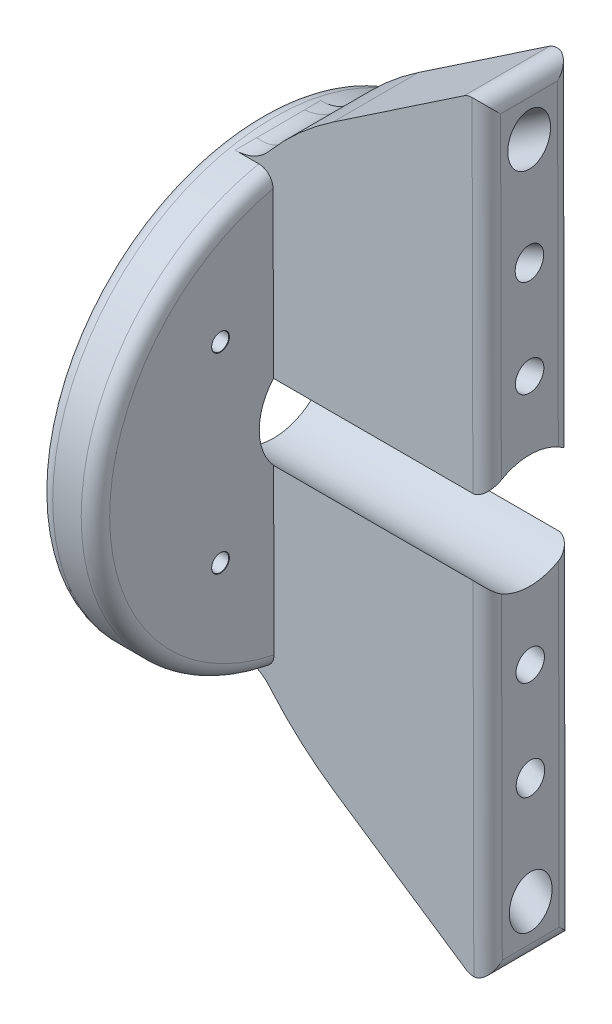
SolidWorks part; units mm, degrees
note: '?' marks a value the reader was unsure of.
ref_plane "前视基准面" through (0, 0, 0) normal (0, 0, 1) x (1, 0, 0)
ref_plane "上视基准面" through (0, 0, 0) normal (0, 1, 0) x (1, 0, 0)
ref_plane "右视基准面" through (0, 0, 0) normal (1, 0, 0) x (0, 0, -1)
other "图形1"
sketch "草图5" plane through (-19, 0, 0) normal (-1, 0, 0) x (0, 0, 1)
  circle A0 centre (0, 0) radius 15.5
  dimension "D1" = 31
extrude "凸台-拉伸3" add sketch "草图5" against normal blind 4
ref_axis "基准轴1" through (0, -27.6387, 2) along (0, 0, -1)?
ref_plane "基准面1" through (0, 0.0045, -2.0046) normal (0, 0.0023, -1) x (0, 1, 0.0023)
ref_point "点1"
ref_axis "基准轴2" through (0, 27.6387, 2) along (0, 0, -1)?
ref_axis "基准轴3" through (-19, 14.825, 17.05) along (0, 0, -1)?
ref_point "点2"
ref_point "点3"
ref_axis "基准轴4" through (-19, -14.825, -17.05) along (0, 0, 1)?
ref_point "点4"
sketch "草图15" plane through (0, 0.0045, -2.0046) normal (0, 0.0023, -1) x (0, 1, 0.0023)
  line L0 (-27.6433, 0) -> (27.6342, 0)
  line L1 (27.6342, 0) -> (14.8205, -19)
  line L2 (14.8205, -19) -> (-14.8296, -19)
  line L3 (-14.8296, -19) -> (-27.6433, 0)
  line L4 (-18.7273, -13.2205) -> (-11.9872, -19)
  line L5 (0, 0) -> (-0.0045, -19) construction
  line L6 (-15.5, -19) -> (15.5, -19) construction
  line L7 (18.721, -13.2295) -> (11.9781, -19.0057)
extrude "凸台-拉伸4" add sketch "草图15" against normal blind 5 and the other way blind 1 contours L5 L0 L3 L4 L2 | L0 L5 L2 L7 L1
sketch "草图16" plane through (0, 0, 0) normal (1, 0, 0) x (0, 0, -1)
  line L0 (-2.9954, -0.0113) -> (2.0046, -0.0113) construction
  line L2 (2.0265, -9.706) -> (1.9827, 9.7151) construction
  line L3 (-2.933, -27.65) -> (-3.0578, 27.6274) construction
  circle A0 centre (0, 0) radius 4
  point P2 (0, 0)
  dimension "D1" = 8
extrude "切除-拉伸2" cut sketch "草图16" against normal through all
sketch "草图17" plane through (-19, 0, 0) normal (-1, 0, 0) x (0, 0, 1)
  circle A0 centre (0, 0) radius 6
  dimension "D1" = 12
extrude "切除-拉伸3" cut sketch "草图17" against normal blind 1
sketch "草图20" plane through (-15, 0, 0) normal (1, 0, 0) x (0, 0, -1)
  line L0 (-9.5, 0) -> (9.5, 0) construction
  line L1 (0, 9.5) -> (0, -9.5) construction
  line L2 (-6.7175, 6.7175) -> (6.7175, -6.7175) construction
  line L3 (-6.7175, -6.7175) -> (6.7175, 6.7175) construction
  line L4 (0, 9.5) -> (9.5, 0) construction
  circle A0 centre (0, 0) radius 9.5 construction
  circle A1 centre (-6.7175, 6.7175) radius 0.5
  circle A2 centre (6.7175, 6.7175) radius 0.5
  circle A3 centre (6.7175, -6.7175) radius 0.5
  circle A4 centre (-6.7175, -6.7175) radius 0.5
  point P21 (0, 0)
  dimension "D1" = 19
  dimension "D3" = 1
  dimension "D2" = 4
hole_wizard "M1 间隙孔1" positions "草图21" profile "草图22" hole size "M1" standard "GB" end condition through all
sketch "草图21" plane through (-15, 0, 0) normal (1, 0, 0) x (0, 0, -1)
  point P0 (-6.7175, 6.7175)
  point P3 (-6.7175, -6.7175)
  point P6 (6.7175, -6.7175)
  point P9 (6.7175, 6.7175)
sketch "草图22" plane through (-15, 6.7175, 6.7175) normal (0, 1, 0) x (0, 0, -1)
  line L0 (0, 0) -> (0, 4)
  line L1 (0, 4) -> (0.6, 4)
  line L2 (0.6, 4) -> (0.6, 0.025)
  line L3 (0.6, 0.025) -> (0.625, 0)
  line L5 (0.625, 0) -> (0, 0)
  line L6 (-0.6, 0.025) -> (-0.625, 0) construction
  line L11 (0, -6.35) -> (0, 107.95) construction
  dimension "通孔孔直径" = 1.2
  dimension "通孔孔深度" = 4
  dimension "近端锥形沉头孔直径" = 1.25
  dimension "近端锥形沉头孔角度" = 90
sketch "草图23" plane through (0, 0, 0) normal (1, 0, 0) x (0, 0, -1)
  line L0 (-0.0578, 27.6342) -> (0.067, -27.6432) construction
  line L1 (2.9422, 27.6409) -> (-3.0578, 27.6274) construction
  line L2 (3.067, -27.6364) -> (-2.933, -27.65) construction
ref_plane "基准面2" through (0, 0, -0.0046) normal (0, -0.0023, 1) x (1, 0, 0)
ref_plane "基准面3" through (1.7861, 1.2047, 0) normal (0.829, 0.5592, 0) x (0, 0, -1)
ref_axis "基准轴5" through (0.8119, 2.649, 0.0014) along (-0.5592, 0.829, 0.0019)?
ref_axis "基准轴6" through (-10.1183, 16.3658, 0.0001) along (0.829, 0.5592, 0)?
ref_plane "基准面5" through (-6.9229, -3.0823, 0) normal (0.9135, 0.4067, 0) x (0, 0, -1)
ref_plane "基准面6" through (-12.1504, -2.6937, 0) normal (0.9763, 0.2164, 0) x (0, 0, -1)
ref_axis "基准轴7" through (0.8119, -20.455, -0.0508) along (-0.4067, 0.9135, 0.0021)?
ref_axis "基准轴8" through (-6.0049, -30.4145, -0.0733) along (-0.2164, 0.9763, 0.0022)?
sketch "草图28" plane through (0, 0, -0.0046) normal (0, -0.0023, 1) x (1, 0, 0)
  line L0 (-12.131, 21.8377) -> (-1.5208, 6.1074) construction
  line L1 (0.8119, 2.649) -> (-17.0503, 29.1309) construction
  line L2 (-8.1263, 15.9005) -> (-9.8039, 18.3876)
  line L3 (-8.1263, 15.9005) -> (1.8222, 22.6108)
  line L4 (-9.8039, 18.3876) -> (0.1446, 25.0979)
  line L5 (1.8222, 22.6108) -> (0.1446, 25.0979)
  line L6 (-13.0242, 10.6214) -> (4.838, -29.4978) construction
  line L7 (-14.9845, 10.0899) -> (-3.939, -39.733) construction
  line L8 (0.8119, -20.455) -> (-17.0503, 19.6642) construction
  line L9 (-6.0049, -30.4146) -> (-17.0503, 19.4083) construction
  line L14 (-13.7902, 4.703) -> (-14.2231, 6.6556)
  line L15 (-13.7902, 4.703) -> (1.8305, 8.166)
  line L16 (-14.2231, 6.6556) -> (1.3976, 10.1186)
  line L17 (1.8305, 8.166) -> (1.3976, 10.1186)
  line L18 (-13.7902, -4.703) -> (-14.2231, -6.6556)
  line L19 (1.8305, -8.166) -> (1.3976, -10.1186)
  line L20 (-13.7902, -4.703) -> (1.8305, -8.166)
  line L21 (-14.2231, -6.6556) -> (1.3976, -10.1186)
  line L22 (-12.3429, -9.0912) -> (-13.1564, -10.9183)
  line L23 (-12.3429, 9.0912) -> (-13.1564, 10.9183)
  line L24 (-12.3429, 9.0912) -> (1.3603, 15.1922)
  line L25 (-13.1564, 10.9183) -> (0.5468, 17.0193)
  line L26 (1.3603, 15.1922) -> (0.5468, 17.0193)
  line L27 (0, 0) -> (-20.7692, 0) construction
  line L28 (1.3603, -15.1922) -> (0.5468, -17.0193)
  line L29 (-12.3429, -9.0912) -> (1.3603, -15.1922)
  line L30 (-13.1564, -10.9183) -> (0.5468, -17.0193)
  line L31 (-8.1263, -15.9005) -> (-9.8039, -18.3876)
  line L32 (-9.8039, -18.3876) -> (0.1446, -25.0979)
  line L33 (1.8222, -22.6108) -> (0.1446, -25.0979)
  line L34 (-8.1263, -15.9005) -> (1.8222, -22.6108)
  line L35 (0.9834, 23.8543) -> (-8.9651, 17.144)
  line L36 (0.9535, 16.1058) -> (-12.7497, 10.0048)
  line L37 (1.6141, 9.1423) -> (-14.0067, 5.6793)
  line L38 (1.6141, -9.1423) -> (-14.0067, -5.6793)
  line L39 (0.9535, -16.1058) -> (-12.7497, -10.0048)
  line L40 (0.9834, -23.8543) -> (-8.9651, -17.144)
  line L41 (0.9834, 23.8543) -> (3.9997, 25.8889) construction
  line L42 (0.9535, 16.1058) -> (5.7018, 18.2198) construction
  line L43 (1.6141, 9.1423) -> (5.7166, 10.0518) construction
  line L44 (1.6141, -9.1423) -> (22.9193, -13.8656) construction
  line L45 (0.9535, -16.1058) -> (4.9114, -17.8679) construction
  line L46 (0.9834, -23.8543) -> (4.7633, -26.4039) construction
  dimension "D1" = 3
  dimension "D2" = 12
  dimension "D3" = 2
  dimension "D4" = 15
  dimension "D5" = 2
  dimension "D6" = 16
revolve "切除-旋转1" cut sketch "草图28" angle 360 about L41
sketch "草图30" plane through (0, 0, -0.0046) normal (0, -0.0023, 1) x (1, 0, 0)
  line L0 (0.9535, -16.1058) -> (-12.7497, -10.0048) construction
  line L1 (1.6141, -9.1423) -> (-14.0067, -5.6793) construction
  line L2 (1.6141, 9.1423) -> (-14.0067, 5.6793) construction
  line L3 (0.9535, 16.1058) -> (-12.7497, 10.0048) construction
  line L4 (-9.8039, 18.3876) -> (-8.1263, 15.9005)
  line L5 (0.1446, 25.0979) -> (-9.8039, 18.3876)
  line L6 (1.8222, 22.6108) -> (0.1446, 25.0979)
  line L7 (-8.1263, 15.9005) -> (1.8222, 22.6108)
  line L8 (-9.8039, 18.3876) -> (-8.1263, 15.9005)
  line L9 (0.1446, 25.0979) -> (-9.8039, 18.3876)
  line L10 (1.8222, 22.6108) -> (0.1446, 25.0979)
  line L11 (-8.1263, 15.9005) -> (1.8222, 22.6108)
  line L12 (-13.1564, 10.9183) -> (-12.3429, 9.0912)
  line L13 (0.5468, 17.0193) -> (-13.1564, 10.9183)
  line L14 (1.3603, 15.1922) -> (0.5468, 17.0193)
  line L15 (-12.3429, 9.0912) -> (1.3603, 15.1922)
  line L16 (-13.1564, 10.9183) -> (-12.3429, 9.0912)
  line L17 (0.5468, 17.0193) -> (-13.1564, 10.9183)
  line L18 (1.3603, 15.1922) -> (0.5468, 17.0193)
  line L19 (-12.3429, 9.0912) -> (1.3603, 15.1922)
  line L20 (-13.7902, -4.703) -> (-14.2231, -6.6556)
  line L21 (-14.2231, -6.6556) -> (1.3976, -10.1186)
  line L22 (1.3976, -10.1186) -> (1.8305, -8.166)
  line L23 (1.8305, -8.166) -> (-13.7902, -4.703)
  line L24 (-13.7902, -4.703) -> (-14.2231, -6.6556)
  line L25 (-14.2231, -6.6556) -> (1.3976, -10.1186)
  line L26 (1.3976, -10.1186) -> (1.8305, -8.166)
  line L27 (1.8305, -8.166) -> (-13.7902, -4.703)
  line L28 (-14.2231, 6.6556) -> (-13.7902, 4.703)
  line L29 (1.3976, 10.1186) -> (-14.2231, 6.6556)
  line L30 (1.8305, 8.166) -> (1.3976, 10.1186)
  line L31 (-13.7902, 4.703) -> (1.8305, 8.166)
  line L32 (-14.2231, 6.6556) -> (-13.7902, 4.703)
  line L33 (1.3976, 10.1186) -> (-14.2231, 6.6556)
  line L34 (1.8305, 8.166) -> (1.3976, 10.1186)
  line L35 (-13.7902, 4.703) -> (1.8305, 8.166)
  line L36 (-8.1263, -15.9005) -> (-9.8039, -18.3876)
  line L37 (-9.8039, -18.3876) -> (0.1446, -25.0979)
  line L38 (0.1446, -25.0979) -> (1.8222, -22.6108)
  line L39 (1.8222, -22.6108) -> (-8.1263, -15.9005)
  line L40 (-8.1263, -15.9005) -> (-9.8039, -18.3876)
  line L41 (-9.8039, -18.3876) -> (0.1446, -25.0979)
  line L42 (0.1446, -25.0979) -> (1.8222, -22.6108)
  line L43 (1.8222, -22.6108) -> (-8.1263, -15.9005)
  line L44 (0.5468, -17.0193) -> (1.3603, -15.1922)
  line L45 (-13.1564, -10.9183) -> (0.5468, -17.0193)
  line L46 (-12.3429, -9.0912) -> (-13.1564, -10.9183)
  line L47 (1.3603, -15.1922) -> (-12.3429, -9.0912)
  line L48 (0.5468, -17.0193) -> (1.3603, -15.1922)
  line L49 (-13.1564, -10.9183) -> (0.5468, -17.0193)
  line L50 (-12.3429, -9.0912) -> (-13.1564, -10.9183)
  line L51 (1.3603, -15.1922) -> (-12.3429, -9.0912)
  line L52 (0.9834, 23.8543) -> (-8.9651, 17.144) construction
  line L53 (0.9834, -23.8543) -> (-8.9651, -17.144) construction
  line L54 (0.9535, -16.1058) -> (-12.7497, -10.0048)
  line L55 (1.6141, -9.1423) -> (-14.0067, -5.6793)
  line L56 (1.6141, 9.1423) -> (-14.0067, 5.6793)
  line L57 (0.9535, 16.1058) -> (-12.7497, 10.0048)
  line L58 (0.9834, 23.8543) -> (-8.9651, 17.144)
  line L59 (0.9834, -23.8543) -> (-8.9651, -17.144)
  line L60 (0.9535, 16.1058) -> (4.3239, 17.6064) construction
  dimension "D1" = 0
  dimension "D2" = 0
  dimension "D3" = 0
  dimension "D4" = 0
  dimension "D5" = 0
  dimension "D6" = 0
revolve "切除-旋转3" cut sketch "草图30" angle 360 about L60
sketch "草图31" plane through (0, 0, -0.0046) normal (0, -0.0023, 1) x (1, 0, 0)
  line L0 (0.9535, 16.1058) -> (-12.7497, 10.0048) construction
  line L1 (1.6141, 9.1423) -> (-14.0067, 5.6793) construction
  line L2 (1.6141, -9.1423) -> (-14.0067, -5.6793) construction
  line L3 (0.9535, -16.1058) -> (-12.7497, -10.0048) construction
  line L4 (-13.7902, -4.703) -> (-14.2231, -6.6556)
  line L5 (-14.2231, -6.6556) -> (1.3976, -10.1186)
  line L6 (1.3976, -10.1186) -> (1.8305, -8.166)
  line L7 (1.8305, -8.166) -> (-13.7902, -4.703)
  line L8 (-13.7902, -4.703) -> (-14.2231, -6.6556)
  line L9 (-14.2231, -6.6556) -> (1.3976, -10.1186)
  line L10 (1.3976, -10.1186) -> (1.8305, -8.166)
  line L11 (1.8305, -8.166) -> (-13.7902, -4.703)
  line L12 (-13.1564, 10.9183) -> (-12.3429, 9.0912)
  line L13 (-12.3429, 9.0912) -> (1.3603, 15.1922)
  line L14 (1.3603, 15.1922) -> (0.5468, 17.0193)
  line L15 (0.5468, 17.0193) -> (-13.1564, 10.9183)
  line L16 (-13.1564, 10.9183) -> (-12.3429, 9.0912)
  line L17 (-12.3429, 9.0912) -> (1.3603, 15.1922)
  line L18 (1.3603, 15.1922) -> (0.5468, 17.0193)
  line L19 (0.5468, 17.0193) -> (-13.1564, 10.9183)
  line L20 (-9.8039, 18.3876) -> (-8.1263, 15.9005)
  line L21 (-8.1263, 15.9005) -> (1.8222, 22.6108)
  line L22 (1.8222, 22.6108) -> (0.1446, 25.0979)
  line L23 (0.1446, 25.0979) -> (-9.8039, 18.3876)
  line L24 (-9.8039, 18.3876) -> (-8.1263, 15.9005)
  line L25 (-8.1263, 15.9005) -> (1.8222, 22.6108)
  line L26 (1.8222, 22.6108) -> (0.1446, 25.0979)
  line L27 (0.1446, 25.0979) -> (-9.8039, 18.3876)
  line L28 (0.5468, -17.0193) -> (1.3603, -15.1922)
  line L29 (1.3603, -15.1922) -> (-12.3429, -9.0912)
  line L30 (-12.3429, -9.0912) -> (-13.1564, -10.9183)
  line L31 (-13.1564, -10.9183) -> (0.5468, -17.0193)
  line L32 (0.5468, -17.0193) -> (1.3603, -15.1922)
  line L33 (1.3603, -15.1922) -> (-12.3429, -9.0912)
  line L34 (-12.3429, -9.0912) -> (-13.1564, -10.9183)
  line L35 (-13.1564, -10.9183) -> (0.5468, -17.0193)
  line L36 (-9.8039, -18.3876) -> (0.1446, -25.0979)
  line L37 (0.1446, -25.0979) -> (1.8222, -22.6108)
  line L38 (1.8222, -22.6108) -> (-8.1263, -15.9005)
  line L39 (-8.1263, -15.9005) -> (-9.8039, -18.3876)
  line L40 (-9.8039, -18.3876) -> (0.1446, -25.0979)
  line L41 (0.1446, -25.0979) -> (1.8222, -22.6108)
  line L42 (1.8222, -22.6108) -> (-8.1263, -15.9005)
  line L43 (-8.1263, -15.9005) -> (-9.8039, -18.3876)
  line L44 (-13.7902, 4.703) -> (1.8305, 8.166)
  line L45 (-14.2231, 6.6556) -> (-13.7902, 4.703)
  line L46 (1.3976, 10.1186) -> (-14.2231, 6.6556)
  line L47 (1.8305, 8.166) -> (1.3976, 10.1186)
  line L48 (-13.7902, 4.703) -> (1.8305, 8.166)
  line L49 (-14.2231, 6.6556) -> (-13.7902, 4.703)
  line L50 (1.3976, 10.1186) -> (-14.2231, 6.6556)
  line L51 (1.8305, 8.166) -> (1.3976, 10.1186)
  line L52 (0.9834, -23.8543) -> (-8.9651, -17.144) construction
  line L53 (0.9834, 23.8543) -> (-8.9651, 17.144) construction
  line L54 (0.9535, 16.1058) -> (-12.7497, 10.0048)
  line L55 (1.6141, 9.1423) -> (-14.0067, 5.6793)
  line L56 (1.6141, -9.1423) -> (-14.0067, -5.6793)
  line L57 (0.9535, -16.1058) -> (-12.7497, -10.0048)
  line L58 (0.9834, -23.8543) -> (-8.9651, -17.144)
  line L59 (0.9834, 23.8543) -> (-8.9651, 17.144)
  line L60 (1.6141, 9.1423) -> (3.8893, 9.6467) construction
  dimension "D1" = 0
  dimension "D2" = 0
  dimension "D3" = 0
  dimension "D4" = 0
  dimension "D5" = 0
  dimension "D6" = 0
revolve "切除-旋转4" cut sketch "草图31" angle 360 about L60
ref_axis "基准轴10" through (0, 0, 0) along (1, 0, 0)?
ref_plane "基准面7" through (0, 0, 0) normal (0, -1, -0.0023) x (1, 0, 0)
fillet "圆角1" radius 1 3 edges at (-19, 0, 15.5) (-15, 0.035, -15.5) (-15, -0.035, 15.5)
fillet "圆角2" radius 1 6 edges at (0, 27.6342, 0.0578) (0, 15.1358, 3.0296) (0, 15.1441, -2.9704) (0, -15.1538, 2.9612) (0, -15.1351, -3.0388) (0, -27.6432, -0.067)
fillet "圆角3" radius 22 2 edges at (-13.2473, 18.7002, 0.0376) (-13.2205, -18.7272, -0.0469)
fillet "圆角4" radius 3 2 edges at (-15.9887, 15.5, 0.0303) (-15.9879, -15.4999, -0.0397)
ref_axis "基准轴11" through (0, 0, 0) along (1, 0, 0)?
ref_plane "基准面8" through (0, 0, 0) normal (0, -1, -0.0023) x (1, 0, 0)
mirror "镜向1" about plane through (0, 0, 0) normal (0, -1, -0.0023) of "切除-旋转4", "切除-旋转3", "切除-旋转1"
